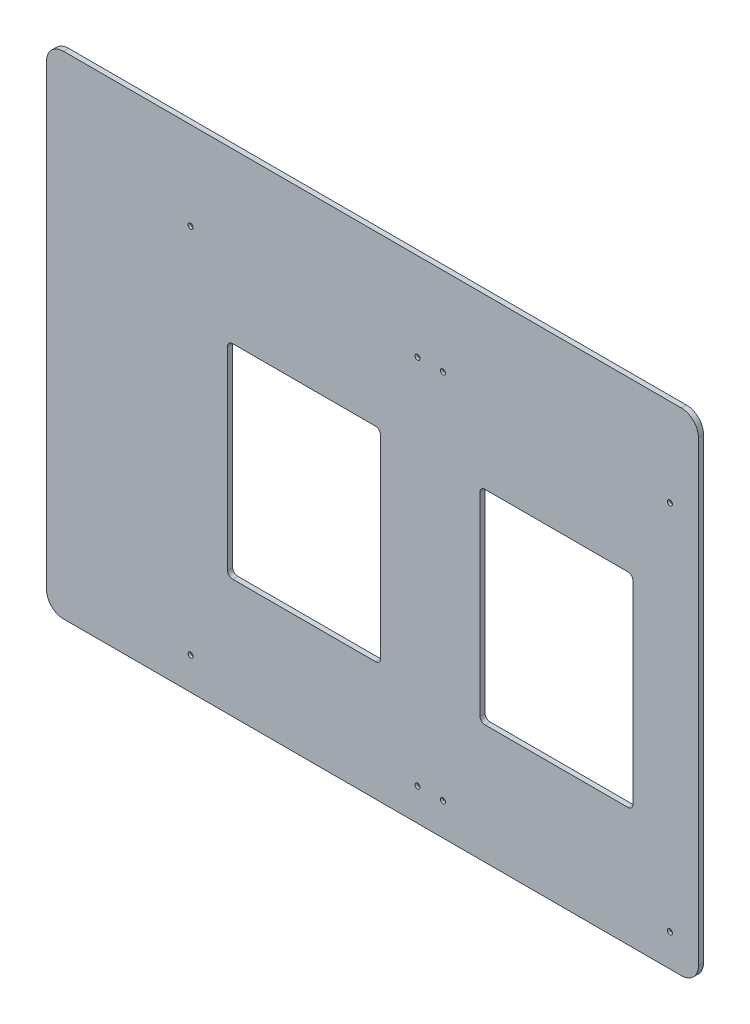
SolidWorks part; units mm, degrees
ref_plane "前视基准面" through (0, 0, 0) normal (0, 0, 1) x (1, 0, 0)
ref_plane "上视基准面" through (0, 0, 0) normal (0, 1, 0) x (1, 0, 0)
ref_plane "右视基准面" through (0, 0, 0) normal (1, 0, 0) x (0, 0, -1)
other "Configuration Table"
sketch "草图1" plane through (0, 0, 0) normal (0, 0, 1) x (1, 0, 0)
  line L0 (151.5, 0) -> (292.5, 0)
  line L1 (3, 0) -> (144, 0)
  line L2 (0, -3) -> (0, -237)
  line L3 (3, -240) -> (144, -240)
  line L4 (147, -3) -> (147, -237)
  line L5 (31.5, -60) -> (115.5, -60)
  line L6 (28.5, -63) -> (28.5, -177)
  line L7 (31.5, -180) -> (115.5, -180)
  line L8 (118.5, -63) -> (118.5, -177)
  line L9 (148.5, -3) -> (148.5, -237)
  line L10 (151.5, -240) -> (292.5, -240)
  line L11 (295.5, -3) -> (295.5, -237)
  line L12 (180, -60) -> (264, -60)
  line L13 (177, -63) -> (177, -177)
  line L14 (180, -180) -> (264, -180)
  line L15 (267, -63) -> (267, -177)
  line L17 (5, -10) -> (142, -10)
  line L18 (-65, -151.5) -> (-8, -151.5)
  line L19 (-68, -148.5) -> (-68, -91.5)
  line L20 (-65, -88.5) -> (-8, -88.5)
  line L21 (-5, -148.5) -> (-5, -91.5)
  line L22 (-68, -151.5) -> (-5, -88.5) construction
  line L23 (-68, -88.5) -> (-5, -151.5) construction
  line L24 (5, -10) -> (5, -230)
  line L25 (-68, 39.2) -> (295.5, 39.2)
  line L26 (-78, 29.2) -> (-78, -240)
  line L27 (-68, -250) -> (295.5, -250)
  line L28 (305.5, 29.2) -> (305.5, -240)
  line L29 (5, -230) -> (142, -230)
  line L30 (142, -10) -> (142, -230)
  line L31 (153.5, -10) -> (290.5, -10)
  line L32 (153.5, -10) -> (153.5, -230)
  line L33 (153.5, -230) -> (290.5, -230)
  line L34 (290.5, -10) -> (290.5, -230)
  line L42 (61.85, 29.2) -> (85.15, 29.2)
  line L43 (60.85, 28.2) -> (60.85, 6)
  line L44 (61.85, 5) -> (85.15, 5)
  line L45 (86.15, 28.2) -> (86.15, 6)
  line L46 (69, 25) -> (78, 25)
  line L47 (69, 25) -> (69, 16)
  line L48 (69, 16) -> (78, 16)
  line L49 (78, 25) -> (78, 16)
  circle A0 centre (6.75, -12.5) radius 1.5
  circle A1 centre (140.25, -12.5) radius 1.5
  circle A2 centre (140.25, -231) radius 1.5
  circle A3 centre (6.75, -231) radius 1.5
  arc A4 (0, -237) -> (3, -240) centre (3, -237) ccw
  arc A5 (144, -240) -> (147, -237) centre (144, -237) ccw
  arc A6 (144, 0) -> (147, -3) centre (144, -3) cw
  arc A7 (3, 0) -> (0, -3) centre (3, -3) ccw
  circle A8 centre (6.75, -12.5) radius 2.25
  circle A9 centre (140.25, -12.5) radius 2.25
  circle A10 centre (140.25, -231) radius 2.25
  circle A11 centre (6.75, -231) radius 2.25
  arc A12 (28.5, -177) -> (31.5, -180) centre (31.5, -177) ccw
  arc A13 (115.5, -180) -> (118.5, -177) centre (115.5, -177) ccw
  arc A14 (115.5, -60) -> (118.5, -63) centre (115.5, -63) cw
  arc A15 (31.5, -60) -> (28.5, -63) centre (31.5, -63) ccw
  circle A16 centre (155.25, -12.5) radius 1.5
  circle A17 centre (288.75, -12.5) radius 1.5
  circle A18 centre (288.75, -231) radius 1.5
  circle A19 centre (155.25, -231) radius 1.5
  arc A20 (148.5, -237) -> (151.5, -240) centre (151.5, -237) ccw
  arc A21 (292.5, -240) -> (295.5, -237) centre (292.5, -237) ccw
  arc A22 (292.5, 0) -> (295.5, -3) centre (292.5, -3) cw
  arc A23 (151.5, 0) -> (148.5, -3) centre (151.5, -3) ccw
  circle A24 centre (155.25, -12.5) radius 2.25
  circle A25 centre (288.75, -12.5) radius 2.25
  circle A26 centre (288.75, -231) radius 2.25
  circle A27 centre (155.25, -231) radius 2.25
  arc A28 (177, -177) -> (180, -180) centre (180, -177) ccw
  arc A29 (264, -180) -> (267, -177) centre (264, -177) ccw
  arc A30 (264, -60) -> (267, -63) centre (264, -63) cw
  arc A31 (180, -60) -> (177, -63) centre (180, -63) ccw
  circle A32 centre (-58, -98.5) radius 2.25
  circle A36 centre (-36.5, -120) radius 26.5
  arc A37 (-65, -151.5) -> (-68, -148.5) centre (-65, -148.5) cw
  arc A38 (-8, -151.5) -> (-5, -148.5) centre (-8, -148.5) ccw
  arc A39 (-8, -88.5) -> (-5, -91.5) centre (-8, -91.5) cw
  arc A40 (-68, -91.5) -> (-65, -88.5) centre (-65, -91.5) cw
  circle A41 centre (-15, -98.5) radius 2.25
  circle A42 centre (-15, -141.5) radius 2.25
  circle A43 centre (-58, -141.5) radius 2.25
  arc A44 (295.5, 39.2) -> (305.5, 29.2) centre (295.5, 29.2) cw
  arc A45 (295.5, -250) -> (305.5, -240) centre (295.5, -240) ccw
  arc A46 (-78, -240) -> (-68, -250) centre (-68, -240) ccw
  arc A47 (-68, 39.2) -> (-78, 29.2) centre (-68, 29.2) ccw
  circle A60 centre (62.85, 27.2) radius 1.25
  circle A61 centre (84.15, 27.2) radius 1.25
  circle A62 centre (84.15, 13.9) radius 1.25
  circle A63 centre (62.85, 13.9) radius 1.25
  arc A64 (61.85, 29.2) -> (60.85, 28.2) centre (61.85, 28.2) ccw
  arc A65 (85.15, 29.2) -> (86.15, 28.2) centre (85.15, 28.2) cw
  arc A66 (85.15, 5) -> (86.15, 6) centre (85.15, 6) ccw
  arc A67 (60.85, 6) -> (61.85, 5) centre (61.85, 6) ccw
  circle A68 centre (62.85, 27.2) radius 1.75
  circle A69 centre (84.15, 27.2) radius 1.75
  circle A70 centre (84.15, 13.9) radius 1.75
  circle A71 centre (62.85, 13.9) radius 1.75
  point P23 (0, 0)
  point P33 (-36.5, -120)
  point P38 (118.5, -180)
  point P41 (118.5, -60)
  point P44 (28.5, -60)
  point P161 (0, 0)
  point P162 (0, 0)
  point P163 (0, 0)
  point P164 (0, 0)
  point P165 (0, 0)
  point P166 (0, 0)
  point P167 (0, 0)
  point P168 (0, 0)
  dimension "D1" = 3
  dimension "D10" = 3
  dimension "D11" = 4.5
  dimension "D18" = 3
  dimension "D9" = 3
  dimension "D22" = 3
  dimension "D23" = 4.5
  dimension "D26" = 3
  dimension "D33" = 4.5
  dimension "D40" = 53
  dimension "D41" = 3
  dimension "D50" = 10
  dimension "D59" = 13.3
  dimension "D69" = 60.85
  dimension "D46" = 21.3
  dimension "D68" = 10
  dimension "D4" = 147
  dimension "D5" = 240
  dimension "D6" = 133.5
  dimension "D7" = 6.75
  dimension "D8" = 218.5
  dimension "D14" = 90
  dimension "D15" = 120
  dimension "D16" = 28.5
  dimension "D17" = 60
  dimension "D19" = 12.5
  dimension "D20" = 133.5
  dimension "D21" = 218.5
  dimension "D24" = 28.5
  dimension "D25" = 60
  dimension "D27" = 147
  dimension "D28" = 6.75
  dimension "D29" = 240
  dimension "D30" = 12.5
  dimension "D31" = 15
  dimension "D32" = 133.5
  dimension "D34" = 10
  dimension "D35" = 10
  dimension "D36" = 2
  dimension "D37" = 2
  dimension "D38" = 43
  dimension "D39" = 10
  dimension "D42" = 5
  dimension "D43" = 88.5
  dimension "D44" = 10
  dimension "D45" = 10
  dimension "D47" = 10
  dimension "D48" = 10
  dimension "D49" = 43
  dimension "D51" = 10
  dimension "D52" = 5
  dimension "D53" = 5
  dimension "D54" = 10
  dimension "D55" = 10
  dimension "D56" = 5
  dimension "D57" = 5
  dimension "D58" = 10
  dimension "D60" = 2
  dimension "D61" = 2
  dimension "D62" = 9
  dimension "D63" = 9
  dimension "D64" = 8.15
  dimension "D65" = 24.2
  dimension "D66" = 25.3
  dimension "D67" = 5
  dimension "D2" = 2
  dimension "D3" = 2
  dimension "D12" = 2
  dimension "D13" = 2
extrude "凸台-拉伸1" add sketch "草图1" along normal blind 3 contours L26 A46 L27 A45 L28 A44 L25 A47
extrude "切除-拉伸1" cut sketch "草图1<3>" along normal blind 1.5 contours A25 | A24 | A9 | A8 | A11 | A10 | A27 | A26
sketch "草图1<3>" plane through (0, 0, 0) normal (0, 0, 1) x (1, 0, 0) same geometry as "草图1"
extrude "切除-拉伸2" cut sketch "草图1<4>" along normal blind 3 contours A18 | A19 | A2 | A3 | A0 | A1 | A16 | A17 | L13 A28 L14 A29 L15 A30 L12 A31 | L8 A13 L7 A12 L6 A15 L5 A14
sketch "草图1<4>" plane through (0, 0, 0) normal (0, 0, 1) x (1, 0, 0) same geometry as "草图1"
